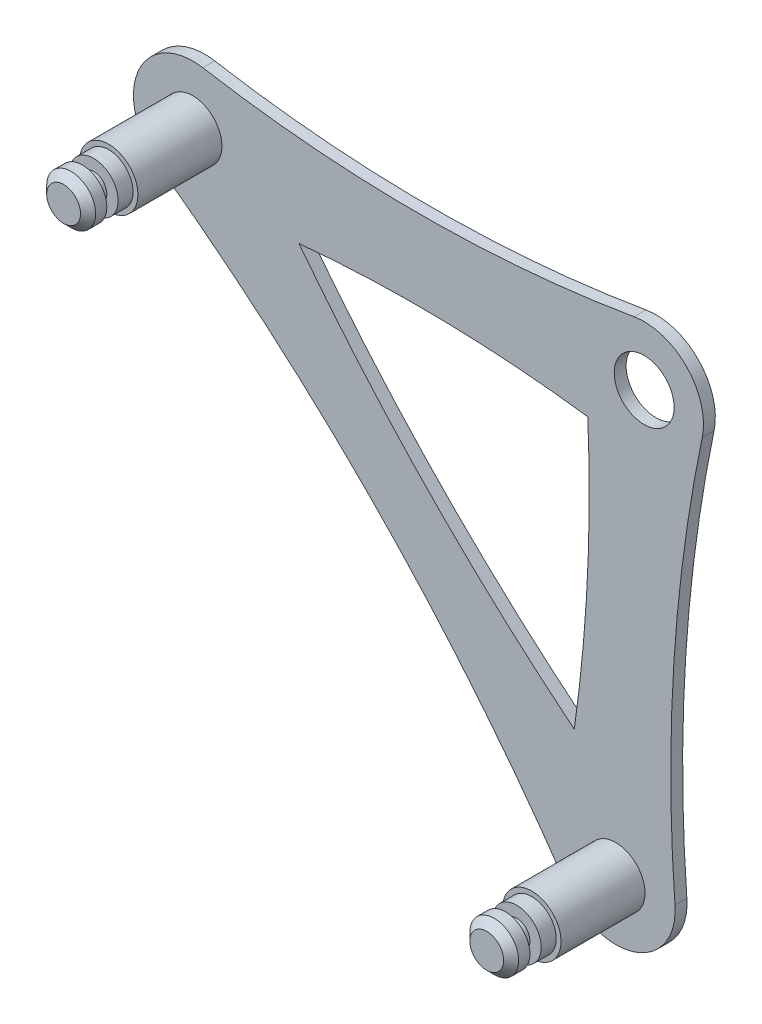
SolidWorks part; units mm, degrees
ref_plane "Plan de face" through (0, 0, 0) normal (1, 0, 0) x (0, 1, 0)
ref_plane "Plan de dessus" through (0, 0, 0) normal (0, 0, 1) x (0, 1, 0)
ref_plane "Plan de droite" through (0, 0, 0) normal (0, 1, 0) x (-1, 0, 0)
sketch "Esquisse1" plane through (0, 0, 0) normal (0, 0, 1) x (0, 1, 0)
  line L0 (0, 0) -> (0, 60.06) construction
  line L1 (0, 60.06) -> (-57.9076, 3.7671) construction
  line L2 (-57.9076, 3.7671) -> (0, 0) construction
  circle A0 centre (0, 60.06) radius 3.885
  circle A1 centre (-57.9076, 3.7671) radius 3.885
  circle A2 centre (0, 0) radius 3.985
  circle A3 centre (-57.9076, 3.7671) radius 7.89
  circle A4 centre (0, 60.06) radius 7.89
  circle A5 centre (0, 0) radius 7.89
  arc A6 (-6.3973, 64.6781) -> (-62.343, 10.2924) centre (-188.8285, 196.3742) cw
  arc A7 (4.4354, 53.5347) -> (-51.5103, -0.851) centre (130.9209, -132.547) ccw
  arc A8 (-57.3159, -4.1007) -> (-1.6061, -7.7248) centre (-42.3173, -203.5375) cw
  arc A9 (-56.3015, 11.4919) -> (-0.5917, 7.8678) centre (-15.5903, 207.3046) ccw
  arc A10 (7.7768, 1.3319) -> (7.7768, 58.7281) centre (175.337, 30.03) cw
  arc A11 (-7.7768, 1.3319) -> (-7.7768, 58.7281) centre (-175.337, 30.03) ccw
  dimension "D4" = 7.97
  dimension "D5" = 7.77
  dimension "D6" = 15.78
  dimension "D7" = 225
  dimension "D8" = 200
  dimension "D9" = 170
  dimension "D1" = 60.06
  dimension "D2" = 80.76
  dimension "D3" = 58.03
extrude "Boss.-Extru.1" add sketch "Esquisse1" along normal blind 1.58 contours A1 | A3 A1 | A9 A3 A7 | A7 A11 A4 A6 A3 A9 | A11 A7 A4 | A4 A0 | A0 | A5 A11 A9 A7 A3 A8 | A11 A9 A5 A10 A4 A7 | A11 A5 A9 | A5 A2 region at (-60.06, 0, 0) region at (-3.7671, -57.9076, 0) region at (-1.4091, -50.6124, 0) region at (-7.3262, -48.7618, 0) region at (-32.2101, -29.3004, 0) region at (-1.4313, -27.8911, 0) region at (-67.3552, 2.3581, 0) region at (-50.991, -3.8805, 0) region at (-28.8224, 0.3783, 0) region at (-6.2192, -5.6647, 0) region at (4.3169, -6.336, 0)
extrude "Boss.-Extru.2" add sketch "Esquisse1<3>" along normal blind 11.18 from surface contours A1 | A0 starting at face at (-20.984, -18.8941, 1.58)
sketch "Esquisse1<3>" plane through (0, 0, 0) normal (0, 0, 1) x (0, 1, 0) same geometry as "Esquisse1"
sketch "Esquisse2" plane through (0, 0, 12.76) normal (0, 0, 1) x (1, 0, 0)
  circle A2 centre (-3.7671, -57.9076) radius 3.25
  circle A3 centre (-60.06, 0) radius 3.25
  dimension "D1" = 6.5
extrude "Boss.-Extru.3" add sketch "Esquisse2" along normal blind 6
sketch "Esquisse3" plane through (0, 0, 18.76) normal (0, 0, 1) x (1, 0, 0)
  circle A2 centre (-60.06, 0) radius 1.75
  circle A3 centre (-60.06, 0) radius 1.75
  circle A5 centre (-3.7671, -57.9076) radius 1.75
  circle A6 centre (-3.7671, -57.9076) radius 1.75
  circle A7 centre (-3.7671, -57.9076) radius 3.25
  circle A8 centre (-3.7671, -57.9076) radius 3.25
  circle M3 centre (-60.06, 0) radius 3.25
  dimension "D1" = 1.5
  dimension "D2" = 1.5
  dimension "D3" = 0
extrude "Enlèv. mat.-Extru.1" cut sketch "Esquisse3" against normal blind 1.5 from offset 2.5 contours A3 M3 | A8 A6 region at (-6.9252, -57.9076, 18.76) region at (-63.2181, 0, 18.76) offset against normal yes
chamfer "Chanfrein1" distance 1 angle 45 2 edges at (-56.81, 0, 18.76) (-0.5171, -57.9076, 18.76)
